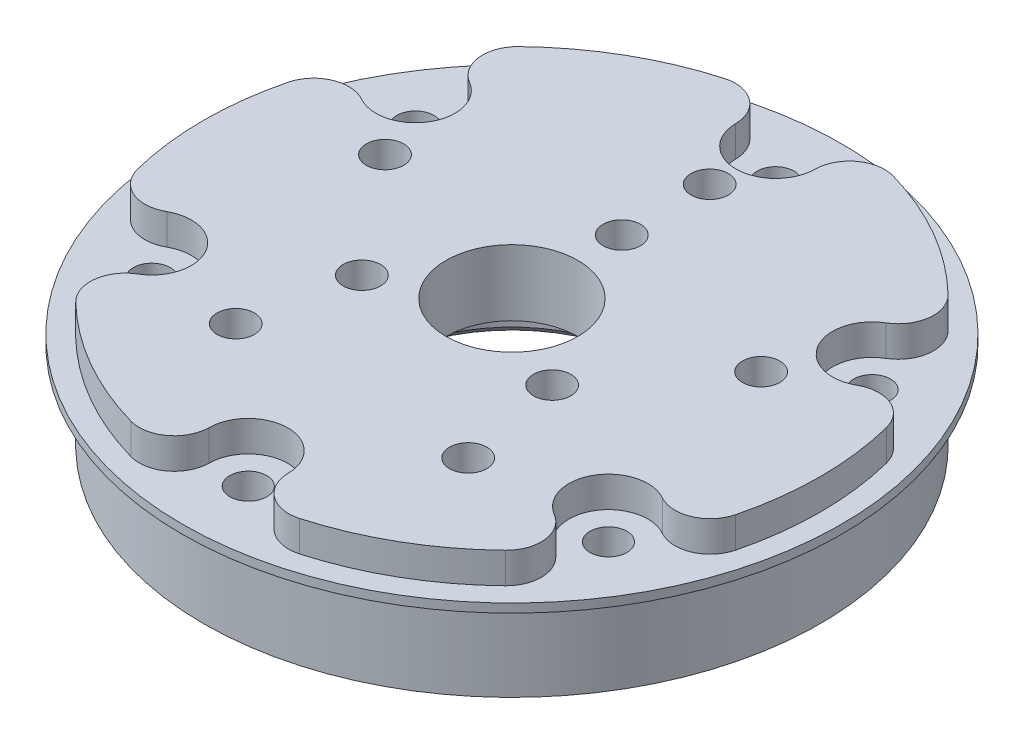
SolidWorks part; units mm, degrees
ref_plane "Front Plane" through (0, 0, 0) normal (0, 0, 1) x (1, 0, 0)
ref_plane "Top Plane" through (0, 0, 0) normal (0, 1, 0) x (1, 0, 0)
ref_plane "Right Plane" through (0, 0, 0) normal (1, 0, 0) x (0, 0, -1)
sketch "Sketch1" plane through (0, 0, 0) normal (0, 1, 0) x (1, 0, 0)
  circle A0 centre (0, 0) radius 35.1
  circle A1 centre (0, 0) radius 30 construction
  circle A2 centre (0, 30) radius 2.1
  circle A3 centre (25.9808, 15) radius 2.1
  circle A4 centre (25.9808, -15) radius 2.1
  circle A5 centre (0, -30) radius 2.1
  circle A6 centre (-25.9808, -15) radius 2.1
  circle A7 centre (-25.9808, 15) radius 2.1
  circle A9 centre (0, 0) radius 37.5
  point P18 (0, 0)
  dimension "D1" = 70.2
  dimension "D2" = 60
  dimension "D3" = 4.2
  dimension "D4" = 6
  dimension "D5" = 75
extrude "Boss-Extrude1" add sketch "Sketch1" along normal blind 14.5 contours A7 | A2 | A3 | A4 | A5 | A0 | A6 region at (0, 0, -30) region at (25.9808, 0, -15) region at (25.9808, 0, 15) region at (0, 0, 30) region at (-25.9808, 0, -15)
extrude "Boss-Extrude2" add sketch "Sketch1<3>" along normal blind 1 from offset 10 contours A6 | A7 | A2 | A4 | A9 | A3 | A5 region at (0, 0, -30) region at (25.9808, 0, 15) region at (-25.9808, 0, 15) region at (-25.9808, 0, -15)
sketch "Sketch1<3>" plane through (0, 0, 0) normal (0, 1, 0) x (1, 0, 0) same geometry as "Sketch1"
sketch "Sketch2" plane through (0, 14.5, 0) normal (0, 1, 0) x (1, 0, 0)
  circle A0 centre (0, 0) radius 22.5 construction
  circle A1 centre (0, 22.5) radius 2.125
  circle A2 centre (21.3988, 6.9529) radius 2.125
  circle A3 centre (13.2252, -18.2029) radius 2.125
  circle A4 centre (-13.2252, -18.2029) radius 2.125
  circle A5 centre (-21.3988, 6.9529) radius 2.125
  circle A6 centre (0, 0) radius 12.5 construction
  circle A7 centre (0, 12.5) radius 2.125
  circle A8 centre (10.8253, -6.25) radius 2.125
  circle A9 centre (-10.8253, -6.25) radius 2.125
  circle A10 centre (0, 0) radius 7.5
  point P15 (0, 0)
  point P23 (0, 0)
  dimension "D1" = 45
  dimension "D2" = 4.25
  dimension "D3" = 5
  dimension "D4" = 25
  dimension "D5" = 3
  dimension "D6" = 15
extrude "Cut-Extrude1" cut sketch "Sketch2" against normal through all
sketch "Sketch3" plane through (0, 14.5, 0) normal (0, 1, 0) x (1, 0, 0)
  line L37 (4.5, 30) -> (4.5, 34.8103)
  line L38 (-4.5, 30) -> (-4.5, 34.8103)
  line L39 (28.2308, 11.1029) -> (32.3966, 13.5081)
  line L40 (23.7308, 18.8971) -> (27.8966, 21.3023)
  line L41 (23.7308, -18.8971) -> (27.8966, -21.3023)
  line L42 (28.2308, -11.1029) -> (32.3966, -13.5081)
  line L43 (-4.5, -30) -> (-4.5, -34.8103)
  line L44 (4.5, -30) -> (4.5, -34.8103)
  line L45 (-28.2308, -11.1029) -> (-32.3966, -13.5081)
  line L46 (-23.7308, -18.8971) -> (-27.8966, -21.3023)
  line L47 (-23.7308, 18.8971) -> (-27.8966, 21.3023)
  line L48 (-28.2308, 11.1029) -> (-32.3966, 13.5081)
  arc A6 (-4.5, 30) -> (4.5, 30) centre (0, 30) ccw
  circle A7 centre (0, 0) radius 35.1 construction
  arc A8 (4.5, 34.8103) -> (-4.5, 34.8103) centre (0, 0) ccw
  arc A9 (23.7308, 18.8971) -> (28.2308, 11.1029) centre (25.9808, 15) ccw
  arc A10 (32.3966, 13.5081) -> (27.8966, 21.3023) centre (0, 0) ccw
  arc A11 (28.2308, -11.1029) -> (23.7308, -18.8971) centre (25.9808, -15) ccw
  arc A12 (27.8966, -21.3023) -> (32.3966, -13.5081) centre (0, 0) ccw
  arc A13 (4.5, -30) -> (-4.5, -30) centre (0, -30) ccw
  arc A14 (-4.5, -34.8103) -> (4.5, -34.8103) centre (0, 0) ccw
  arc A15 (-23.7308, -18.8971) -> (-28.2308, -11.1029) centre (-25.9808, -15) ccw
  arc A16 (-32.3966, -13.5081) -> (-27.8966, -21.3023) centre (0, 0) ccw
  arc A17 (-28.2308, 11.1029) -> (-23.7308, 18.8971) centre (-25.9808, 15) ccw
  arc A18 (-27.8966, 21.3023) -> (-32.3966, 13.5081) centre (0, 0) ccw
  point P34 (0, 0)
  dimension "D1" = 9
extrude "Cut-Extrude2" cut sketch "Sketch3" against normal blind 3.5
fillet "Fillet1" radius 4 12 edges at (-32.3966, 12.75, 13.5081) (-27.8966, 12.75, 21.3023) (-4.5, 12.75, 34.8103) (4.5, 12.75, 34.8103) (27.8966, 12.75, 21.3023) (32.3966, 12.75, 13.5081) (32.3966, 12.75, -13.5081) (27.8966, 12.75, -21.3023) (4.5, 12.75, -34.8103) (-4.5, 12.75, -34.8103) (-32.3966, 12.75, -13.5081) (-27.8966, 12.75, -21.3023)
sketch "Sketch4" plane through (0, 0, 0) normal (0, -1, 0) x (1, 0, 0)
  circle A0 centre (0, 0) radius 15.1
  dimension "D1" = 30.2
extrude "Cut-Extrude3" cut sketch "Sketch4" against normal blind 7
sketch "Sketch5" plane through (0, 0, 0) normal (0, -1, 0) x (1, 0, 0)
  line L0 (-17.613, 18.2029) -> (-8.8373, 18.2029) construction
  line L1 (-11.0312, 22.0029) -> (-15.4191, 22.0029)
  line L2 (-15.4191, 22.0029) -> (-17.613, 18.2029)
  line L3 (-17.613, 18.2029) -> (-15.4191, 14.4029)
  line L4 (-15.4191, 14.4029) -> (-11.0312, 14.4029)
  line L5 (-11.0312, 14.4029) -> (-8.8373, 18.2029)
  line L6 (-8.8373, 18.2029) -> (-11.0312, 22.0029)
  line L7 (17.5171, 17.2906) -> (16.1612, 21.4637)
  line L8 (16.1612, 21.4637) -> (11.8692, 22.376)
  line L9 (11.8692, 22.376) -> (8.9332, 19.1152)
  line L10 (8.9332, 19.1152) -> (10.2891, 14.9421)
  line L11 (10.2891, 14.9421) -> (14.5811, 14.0298)
  line L12 (14.5811, 14.0298) -> (17.5171, 17.2906)
  line L13 (11.8692, 22.376) -> (14.5811, 14.0298) construction
  line L14 (21.8574, -11.3167) -> (25.4073, -8.7376)
  line L15 (25.4073, -8.7376) -> (24.9486, -4.3738)
  line L16 (24.9486, -4.3738) -> (20.9401, -2.5891)
  line L17 (20.9401, -2.5891) -> (17.3903, -5.1682)
  line L18 (17.3903, -5.1682) -> (17.8489, -9.532)
  line L19 (17.8489, -9.532) -> (21.8574, -11.3167)
  line L20 (24.9486, -4.3738) -> (17.8489, -9.532) construction
  line L21 (-4.0085, -24.2847) -> (-0.4587, -26.8638)
  line L22 (-0.4587, -26.8638) -> (3.5499, -25.0791)
  line L23 (3.5499, -25.0791) -> (4.0085, -20.7153)
  line L24 (4.0085, -20.7153) -> (0.4587, -18.1362)
  line L25 (0.4587, -18.1362) -> (-3.5499, -19.9209)
  line L26 (-3.5499, -19.9209) -> (-4.0085, -24.2847)
  line L27 (3.5499, -25.0791) -> (-3.5499, -19.9209) construction
  line L28 (-24.3348, -3.6921) -> (-25.6907, -7.8652)
  line L29 (-25.6907, -7.8652) -> (-22.7547, -11.126)
  line L30 (-22.7547, -11.126) -> (-18.4627, -10.2137)
  line L31 (-18.4627, -10.2137) -> (-17.1068, -6.0406)
  line L32 (-17.1068, -6.0406) -> (-20.0428, -2.7798)
  line L33 (-20.0428, -2.7798) -> (-24.3348, -3.6921)
  line L34 (-22.7547, -11.126) -> (-20.0428, -2.7798) construction
  circle A0 centre (-13.2252, 18.2029) radius 3.8 construction
  circle A1 centre (13.2252, 18.2029) radius 3.8 construction
  circle A2 centre (21.3988, -6.9529) radius 3.8 construction
  circle A3 centre (0, -22.5) radius 3.8 construction
  circle A4 centre (-21.3988, -6.9529) radius 3.8 construction
  point P44 (0, 0)
  dimension "D1" = 7.6
  dimension "D2" = 5
extrude "Cut-Extrude4" cut sketch "Sketch5" against normal blind 3.2
chamfer "Chamfer1" distance 1 angle 45 1 edges at (0, 0, -15.1)
